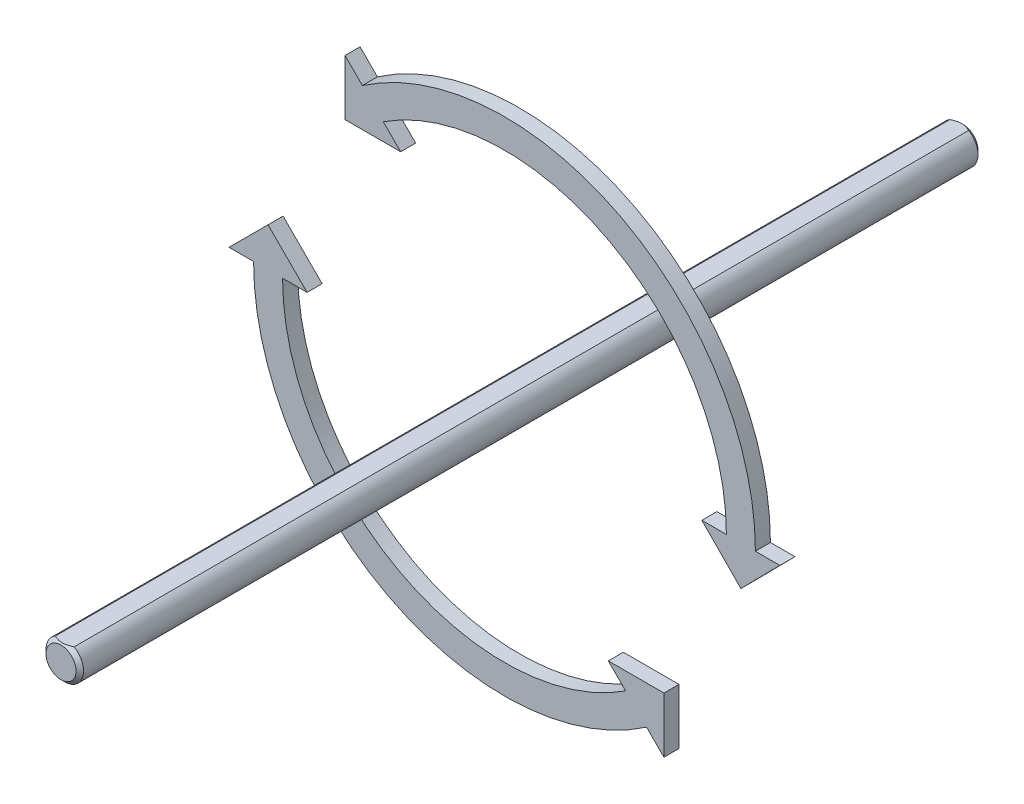
SolidWorks part; units mm, degrees
material "Plain Carbon Steel"
ref_plane "Front" through (0, 0, 0) normal (0, 0, 1) x (1, 0, 0)
ref_plane "Top" through (0, 0, 0) normal (0, 1, 0) x (1, 0, 0)
ref_plane "Right" through (0, 0, 0) normal (1, 0, 0) x (0, 0, -1)
sketch "Sketch1" plane through (0, 0, 0) normal (0, 0, 1) x (1, 0, 0)
  circle A0 centre (0, 0) radius 3.175
  dimension "D1" = 6.35
extrude "Extrude1" add sketch "Sketch1" along normal mid plane 152.4
chamfer "Chamfer1" distance 0.635 angle 45 2 edges at (3.175, 0, -76.2) (3.175, 0, 76.2)
sketch "Sketch13" plane through (0, 0, 0) normal (0, 0, 1) x (1, 0, 0)
  line L3 (-1.5875, 2.7496) -> (1.5875, 2.7496)
  circle A0 centre (0, 0) radius 3.175 construction
  arc A1 (1.5875, 2.7496) -> (-1.5875, 2.7496) centre (0, 0) ccw
  dimension "D1" = 3.175
extrude "Extrude7" cut sketch "Sketch13" against normal through all and the other way through all
ref_axis "Axis1" through (0, 0, 0) along (0, 0, 1)
ref_point "Point1"
sketch "Sketch15" plane through (0, 0, 0) normal (0, 0, 1) x (1, 0, 0)
  line L0 (1.5875, 2.7496) -> (-1.5875, 2.7496) construction
  line L1 (1.5875, 2.7496) -> (-1.5875, 2.7496)
  arc A0 (-1.5875, 2.7496) -> (1.5875, 2.7496) centre (0, 0) ccw construction
  arc A1 (-1.5875, 2.7496) -> (1.5875, 2.7496) centre (0, 0) ccw
ref_plane "Plane1" through (0, 0, 0) normal (0, 0, 1) x (1, 0, 0)
sketch "Sketch16" plane through (0, 0, 0) normal (0, 0, 1) x (1, 0, 0)
  line L4 (-17.5427, 28.4796) -> (-20.4753, 31.4122)
  line L5 (-26.9402, 37.8772) -> (-26.9402, 28.4796)
  line L6 (-26.9402, 28.4796) -> (-17.5427, 28.4796)
  line L7 (17.5427, -28.4796) -> (20.4753, -31.4122)
  line L8 (26.9402, -37.8772) -> (26.9402, -28.4796)
  line L9 (26.9402, -28.4796) -> (17.5427, -28.4796)
  line L10 (-24.0077, 34.9446) -> (-26.9402, 37.8772)
  line L11 (24.0077, -34.9446) -> (26.9402, -37.8772)
  line L12 (37.4962, 0) -> (33.3489, 0)
  line L13 (33.3489, 0) -> (39.9465, -6.6922)
  line L14 (39.9465, -6.6922) -> (46.5441, 0)
  line L15 (46.5441, 0) -> (42.3969, 0)
  line L16 (-37.4962, 0) -> (-33.3489, 0)
  line L17 (-33.3489, 0) -> (-39.9465, 6.5976)
  line L18 (-39.9465, 6.5976) -> (-46.5441, 0)
  line L19 (-46.5441, 0) -> (-42.3969, 0)
  arc A0 (42.3969, 0) -> (-24.0077, 34.9446) centre (0, 0) ccw
  arc A1 (37.4962, 0) -> (-20.4753, 31.4122) centre (0, 0) ccw
  arc A2 (-37.4962, 0) -> (20.4753, -31.4122) centre (0, 0) ccw
  arc A3 (-42.3969, 0) -> (24.0077, -34.9446) centre (0, 0) ccw
  point P13 (-3.4962, 4.2045)
  point P17 (3.8666, -3.8666)
extrude "Boss-Extrude1" add sketch "Sketch16" along normal blind 1.27 and the other way blind 1.27 separate body
equation "\"D1@Chamfer1\" = \"D1@Sketch1\" * .1"
equation "\"D1@Sketch13\" = \"D1@Sketch1\" * .5"
